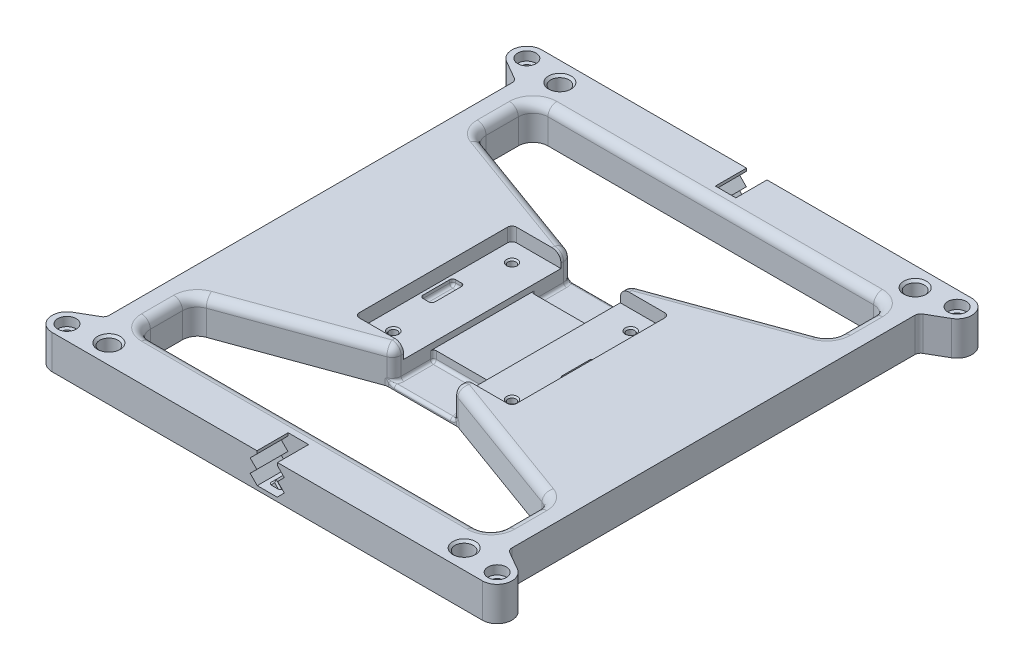
SolidWorks part; units mm, degrees
ref_plane "Front Plane" through (0, 0, 0) normal (0, 0, 1) x (1, 0, 0)
ref_plane "Top Plane" through (0, 0, 0) normal (0, 1, 0) x (1, 0, 0)
ref_plane "Right Plane" through (0, 0, 0) normal (1, 0, 0) x (0, 0, -1)
sketch "Sketch1" plane through (0, 0, 0) normal (0, 1, 0) x (1, 0, 0)
  line L0 (0, 0) -> (0, 67.5) construction
  line L1 (0, 67.5) -> (-67.875, 67.5) construction
  line L2 (-67.875, 67.5) -> (-67.875, 0)
  line L3 (-67.875, 0) -> (67.875, 0)
  line L4 (-67.875, 67.5) -> (-67.875, 80.5)
  line L5 (-65.875, 82.5) -> (65.875, 82.5)
  line L6 (0, 82.5) -> (0, 67.5) construction
  line L9 (67.875, 67.5) -> (67.875, 80.5)
  line L10 (67.875, 67.5) -> (67.875, 0)
  line L14 (-67.875, 70.5) -> (0, 70.5) construction
  circle A1 centre (-59.875, 76) radius 3.075 construction
  arc A11 (-67.875, 80.5) -> (-65.875, 82.5) centre (-65.875, 80.5) cw
  circle A12 centre (59.875, 76) radius 3.075 construction
  arc A13 (67.875, 80.5) -> (65.875, 82.5) centre (65.875, 80.5) ccw
  point P19 (67.875, 82.5)
  point P45 (-67.875, 82.5)
  dimension "D5" = 12
  dimension "D3" = 6.15
  dimension "D4" = 2
  dimension "D1" = 67.875
  dimension "D2" = 67.5
  dimension "D6" = 8
  dimension "D7" = 8.5
  dimension "D8" = 3
  dimension "D11" = 82.5
extrude "Boss-Extrude1" add sketch "Sketch1" along normal blind 11.5
sketch "Sketch3" plane through (0, 11.5, 0) normal (0, 1, 0) x (1, 0, 0)
  line L0 (0, 0) -> (-67.875, 0) construction
  line L2 (0, 0) -> (0, 82.5) construction
  line L3 (65.875, 82.5) -> (-65.875, 82.5) construction
  line L4 (3.96, -16.3) -> (3.96, 16.3)
  line L5 (-2.46, -17.8) -> (2.46, -17.8)
  line L6 (-3.96, 16.3) -> (-3.96, -16.3)
  line L7 (2.46, 17.8) -> (-2.46, 17.8)
  line L8 (0, 17.8) -> (0, -17.8) construction
  line L9 (-67.875, 80.5) -> (-67.875, 0) construction
  line L10 (-67.875, 0) -> (67.875, 0) construction
  arc A0 (-2.46, 17.8) -> (-3.96, 16.3) centre (-2.46, 16.3) ccw
  arc A1 (3.96, 16.3) -> (2.46, 17.8) centre (2.46, 16.3) ccw
  arc A2 (2.46, -17.8) -> (3.96, -16.3) centre (2.46, -16.3) ccw
  arc A3 (-3.96, -16.3) -> (-2.46, -17.8) centre (-2.46, -16.3) ccw
  point P9 (0, 0)
  point P23 (0, 0)
  dimension "D2" = 1.5
  dimension "D1" = 35.6
  dimension "D3" = 7.92
sketch "Sketch4" plane through (0, 11.5, 0) normal (0, 1, 0) x (1, 0, 0)
  circle A3 centre (59.875, 76) radius 3.075 construction
  circle A5 centre (-59.875, 76) radius 3.075 construction
  circle A10 centre (59.875, 76) radius 3.075
  circle A13 centre (-59.875, 76) radius 3.075
extrude "Cut-Extrude1" cut sketch "Sketch4" against normal blind 6
sketch "Sketch40" plane through (0, 0, -82.5) normal (0, 0, -1) x (-1, 0, 0)
  line L1 (5.55, 3.75) -> (3.3, 6) construction
  line L2 (5.55, 3.75) -> (3.3, 1.5) construction
  line L3 (0, 11.5) -> (0, 1.5) construction
  line L4 (0, 1.5) -> (3.3, 1.5) construction
  line L5 (3.3, 6) -> (5.55, 8.25) construction
  line L6 (3.3, 6) -> (3.3, 1.5) construction
  line L7 (5.55, 8.25) -> (3.3, 10.5) construction
  line L8 (3.3, 6) -> (3.3, 10.5) construction
  line L9 (5.55, 3.75) -> (5.55, 8.25) construction
  line L10 (3.3, 10.5) -> (3.3, 11.5) construction
  line L11 (3.3, 1.5) -> (5.55, 1.5) construction
  line L12 (5.55, 1.5) -> (5.55, 3.75) construction
  line L13 (5.55, 3.75) -> (3.3, 3.75) construction
  line L14 (5.55, 8.25) -> (3.3, 8.25) construction
  line L15 (3.3, 6) -> (5.55, 6) construction
  line L16 (-3.3, 11.5) -> (3.3, 11.5)
  line L17 (3.3621, 1.35) -> (-3.3621, 1.35)
  line L18 (0, 1.35) -> (0, 1.5) construction
  line L19 (-3.3, 11.5) -> (-3.45, 11.5)
  line L20 (-3.45, 10.5621) -> (-3.45, 11.5)
  line L22 (3.45, 10.5621) -> (3.45, 11.5)
  line L23 (5.7621, 8.25) -> (3.45, 10.5621)
  line L24 (3.5121, 6) -> (5.7621, 8.25)
  line L25 (5.7621, 3.75) -> (3.5121, 6)
  line L26 (5.7621, 3.75) -> (3.3621, 1.35)
  line L33 (3.3, 11.5) -> (3.45, 11.5)
  line L34 (-65.875, 11.5) -> (65.875, 11.5) construction
  line L35 (-5.7621, 8.25) -> (-3.45, 10.5621)
  line L36 (-3.5121, 6) -> (-5.7621, 8.25)
  line L37 (-5.7621, 3.75) -> (-3.5121, 6)
  line L38 (-5.7621, 3.75) -> (-3.3621, 1.35)
  dimension "D2" = 1
  dimension "D3" = 45
  dimension "D4" = 45
  dimension "D5" = 45
  dimension "D6" = 45
  dimension "D7" = 3.3
  dimension "D1" = 10
  dimension "D8" = 0.15
  dimension "D9" = 0.15
  dimension "D10" = 0.15
  dimension "D11" = 0.15
  dimension "D12" = 0.15
  dimension "D13" = 0.15
extrude "Cut-Extrude31" cut sketch "Sketch40" against normal blind 10.5
sketch "Sketch41" plane through (0, 0, -72) normal (0, 0, -1) x (-1, 0, 0)
  line L0 (0, 1.35) -> (0, 3.35) construction
  line L1 (-3.3621, 1.35) -> (3.3621, 1.35) construction
  line L2 (0, 3.35) -> (2, 1.35)
  line L3 (-3.3621, 1.35) -> (3.3621, 1.35) construction
  line L4 (2, 1.35) -> (-2, 1.35)
  line L5 (0, 3.35) -> (-2, 1.35)
  dimension "D1" = 45
  dimension "D2" = 2
extrude "Boss-Extrude9" add sketch "Sketch41" along normal blind 8
chamfer "Chamfer7" distance 0.5 angle 45 2 edges at (1, 2.35, -80) (-1, 2.35, -80)
mirror "Mirror1" about plane through (0, 0, 0) normal (0, 0, 1) of "Cut-Extrude1", "Boss-Extrude1", "Cut-Extrude31", "Boss-Extrude9", "Chamfer7"
sketch "Sketch28" plane through (0, 11.5, 0) normal (0, 1, 0) x (1, 0, 0)
  line L1 (-26, 26) -> (26, 26) construction
  line L2 (-26, 26) -> (-26, -26) construction
  line L3 (-26, -26) -> (26, -26) construction
  line L4 (26, 26) -> (26, -26) construction
  line L5 (-26, 26) -> (26, -26) construction
  line L6 (-26, -26) -> (26, 26) construction
  line L7 (-25, 26.5) -> (25, 26.5)
  line L8 (-26.5, 25) -> (-26.5, -25)
  line L9 (-25, -26.5) -> (25, -26.5)
  line L10 (26.5, 25) -> (26.5, -25)
  line L11 (-26.5, 26.5) -> (26.5, -26.5) construction
  line L12 (-26.5, -26.5) -> (26.5, 26.5) construction
  arc A0 (-25, -26.5) -> (-26.5, -25) centre (-25, -25) cw
  arc A1 (25, -26.5) -> (26.5, -25) centre (25, -25) ccw
  arc A2 (25, 26.5) -> (26.5, 25) centre (25, 25) cw
  arc A3 (-25, 26.5) -> (-26.5, 25) centre (-25, 25) ccw
  point P0 (0, 0)
  point P6 (0, 0)
  dimension "D4" = 1.5
  dimension "D1" = 52
  dimension "D2" = 0.5
  dimension "D3" = 0.5
extrude "Cut-Extrude21" cut sketch "Sketch28" against normal blind 4.6
sketch "Sketch36" plane through (0, 6.9, 0) normal (0, 1, 0) x (1, 0, 0)
  line L2 (-26, 26) -> (-26, -26) construction
  line L3 (-26, 26) -> (26, 26) construction
  circle A0 centre (-20, 20) radius 1.35
  circle A1 centre (20, 20) radius 1.35
  circle A2 centre (20, -20) radius 1.35
  circle A3 centre (-20, -20) radius 1.35
  point P15 (0, 0)
  dimension "D3" = 2.7
  dimension "D1" = 6
  dimension "D2" = 6
extrude "Cut-Extrude28" cut sketch "Sketch36" against normal blind 5
chamfer "Chamfer6" distance 0.5 angle 45 4 edges at (-20, 6.9, 21.35) (20, 6.9, 21.35) (20, 6.9, -18.65) (-20, 6.9, -18.65)
sketch "Sketch29" plane through (0, 6.9, 0) normal (0, 1, 0) x (1, 0, 0)
  line L0 (0, 0) -> (26.5, 0) construction
  line L5 (0, 0) -> (0, -26.5) construction
  line L6 (-25, -26.5) -> (25, -26.5) construction
  line L7 (26.5, -25) -> (26.5, 25) construction
  line L8 (-10, 26.5) -> (10, 16.5) construction
  line L9 (-10, 16.5) -> (10, 26.5) construction
  line L10 (-10, -16.5) -> (10, -16.5)
  line L11 (-10, -16.5) -> (-10, -26.5)
  line L12 (-10, -26.5) -> (10, -26.5)
  line L13 (10, -16.5) -> (10, -26.5)
  line L14 (-10, -16.5) -> (10, -26.5) construction
  line L15 (-10, -26.5) -> (10, -16.5) construction
  line L16 (10, 16.5) -> (10, 26.5)
  line L17 (-10, 26.5) -> (10, 26.5)
  line L18 (-10, 16.5) -> (-10, 26.5)
  line L19 (-10, 16.5) -> (10, 16.5)
  point P4 (0, -21.5)
  point P17 (0, 21.5)
  dimension "D1" = 20
  dimension "D2" = 10
extrude "Cut-Extrude22" cut sketch "Sketch29" against normal blind 5.5
sketch "Sketch25" plane through (0, 0, 0) normal (0, -1, 0) x (1, 0, 0)
  line L0 (0, 0) -> (67.875, 0) construction
  line L2 (0, 0) -> (0, 82.5) construction
  line L4 (75, 73.1699) -> (68.875, 69.6336)
  line L5 (72.5, 77.5) -> (67.875, 77.5) construction
  line L6 (67.875, 67.9016) -> (67.875, 80.5)
  line L8 (65.875, 82.5) -> (72.5, 82.5)
  line L9 (-72.5, 77.5) -> (-67.875, 77.5) construction
  line L10 (-65.875, 82.5) -> (-72.5, 82.5)
  line L11 (-67.875, 67.9016) -> (-67.875, 80.5)
  line L12 (-75, 73.1699) -> (-68.875, 69.6336)
  line L13 (-72.5, -77.5) -> (-67.875, -77.5) construction
  line L14 (72.5, -77.5) -> (67.875, -77.5) construction
  line L15 (-75, -73.1699) -> (-68.875, -69.6336)
  line L16 (-67.875, -67.9016) -> (-67.875, -80.5)
  line L17 (-65.875, -82.5) -> (-72.5, -82.5)
  line L18 (65.875, -82.5) -> (72.5, -82.5)
  line L19 (67.875, -67.9016) -> (67.875, -80.5)
  line L20 (75, -73.1699) -> (68.875, -69.6336)
  line L21 (67.875, 80.5) -> (67.875, -80.5) construction
  line L22 (65.875, 82.5) -> (-65.875, 82.5) construction
  circle A0 centre (72.5, 77.5) radius 1.7
  arc A1 (75, 73.1699) -> (72.5, 82.5) centre (72.5, 77.5) ccw
  arc A2 (68.875, 69.6336) -> (67.875, 67.9016) centre (69.875, 67.9016) ccw
  arc A17 (67.875, 80.5) -> (65.875, 82.5) centre (65.875, 80.5) ccw
  arc A18 (-67.875, 80.5) -> (-65.875, 82.5) centre (-65.875, 80.5) cw
  arc A19 (-68.875, 69.6336) -> (-67.875, 67.9016) centre (-69.875, 67.9016) cw
  arc A20 (-75, 73.1699) -> (-72.5, 82.5) centre (-72.5, 77.5) cw
  circle A21 centre (-72.5, 77.5) radius 1.7
  circle A22 centre (-72.5, -77.5) radius 1.7
  arc A23 (-75, -73.1699) -> (-72.5, -82.5) centre (-72.5, -77.5) ccw
  arc A24 (-68.875, -69.6336) -> (-67.875, -67.9016) centre (-69.875, -67.9016) ccw
  arc A25 (-67.875, -80.5) -> (-65.875, -82.5) centre (-65.875, -80.5) ccw
  arc A26 (67.875, -80.5) -> (65.875, -82.5) centre (65.875, -80.5) cw
  arc A27 (68.875, -69.6336) -> (67.875, -67.9016) centre (69.875, -67.9016) cw
  arc A28 (75, -73.1699) -> (72.5, -82.5) centre (72.5, -77.5) cw
  circle A29 centre (72.5, -77.5) radius 1.7
  arc A30 (67.875, 80.5) -> (65.875, 82.5) centre (65.875, 80.5) ccw construction
  dimension "D1" = 3.4
  dimension "D2" = 10
  dimension "D6" = 2
  dimension "D3" = 4.625
  dimension "D4" = 60
extrude "Boss-Extrude7" add sketch "Sketch25" against normal up to surface (11.5 mm away) up to face at (0, 11.5, 0)
sketch "Sketch27" plane through (0, 11.5, 0) normal (0, 1, 0) x (1, 0, 0)
  circle A4 centre (-72.5, -77.5) radius 3.1
  circle A5 centre (72.5, -77.5) radius 3.1
  circle A6 centre (-72.5, 77.5) radius 3.1
  circle A7 centre (72.5, 77.5) radius 3.1
  dimension "D1" = 6.2
extrude "Cut-Extrude20" cut sketch "Sketch27" against normal blind 3
sketch "Sketch37" plane through (0, 6.9, 0) normal (0, 1, 0) x (1, 0, 0)
  line L0 (67.875, 0) -> (0, 0) construction
  line L2 (0, 0) -> (-67.875, 0) construction
  line L3 (26.5, -25) -> (26.5, 25) construction
  line L4 (24.5, 5.5) -> (22.5, 5.5)
  line L5 (25.5, 4.5) -> (25.5, -4.5)
  line L6 (24.5, -5.5) -> (22.5, -5.5)
  line L7 (21.5, 4.5) -> (21.5, -4.5)
  line L8 (25.5, 5.5) -> (21.5, -5.5) construction
  line L9 (25.5, -5.5) -> (21.5, 5.5) construction
  line L10 (0, 0) -> (0, 26.5) construction
  line L11 (-10, 16.5) -> (10, 16.5) construction
  line L12 (-24.5, -5.5) -> (-22.5, -5.5)
  line L13 (-25.5, 4.5) -> (-25.5, -4.5)
  line L14 (-24.5, 5.5) -> (-22.5, 5.5)
  line L15 (-21.5, 4.5) -> (-21.5, -4.5)
  line L21 (10, 16.5) -> (10, -16.5)
  line L23 (25, 26.5) -> (-25, 26.5) construction
  line L24 (-10, 16.5) -> (10, 16.5)
  line L25 (-10, 16.5) -> (-10, -16.5)
  line L26 (-10, -16.5) -> (10, -16.5)
  line L27 (67.875, -67.9016) -> (67.875, 67.9016) construction
  arc A0 (22.5, -5.5) -> (21.5, -4.5) centre (22.5, -4.5) cw
  arc A1 (25.5, -4.5) -> (24.5, -5.5) centre (24.5, -4.5) cw
  arc A2 (22.5, 5.5) -> (21.5, 4.5) centre (22.5, 4.5) ccw
  arc A3 (24.5, 5.5) -> (25.5, 4.5) centre (24.5, 4.5) cw
  arc A4 (-22.5, 5.5) -> (-21.5, 4.5) centre (-22.5, 4.5) cw
  arc A5 (-24.5, 5.5) -> (-25.5, 4.5) centre (-24.5, 4.5) ccw
  arc A6 (-22.5, -5.5) -> (-21.5, -4.5) centre (-22.5, -4.5) ccw
  arc A7 (-25.5, -4.5) -> (-24.5, -5.5) centre (-24.5, -4.5) ccw
  point P5 (23.5, 0)
  point P54 (10, 0)
  point P56 (-10, 0)
  dimension "D4" = 1
  dimension "D1" = 11
  dimension "D2" = 4
  dimension "D3" = 3
extrude "Cut-Extrude29" cut sketch "Sketch37" against normal blind 2
fillet "Fillet20" radius 1 16 edges at (25.2071, 4.9, -5.2071) (25.5, 4.9, 0) (25.2071, 4.9, 5.2071) (23.5, 4.9, 5.5) (21.7929, 4.9, 5.2071) (21.5, 4.9, 0) (21.7929, 4.9, -5.2071) (-21.7929, 4.9, -5.2071) (-21.5, 4.9, 0) (-21.7929, 4.9, 5.2071) (-23.5, 4.9, 5.5) (-25.2071, 4.9, 5.2071) (-25.5, 4.9, 0) (-25.2071, 4.9, -5.2071) (23.5, 4.9, -5.5) (-23.5, 4.9, -5.5)
sketch "Sketch38" plane through (0, 11.5, 0) normal (0, 1, 0) x (1, 0, 0)
  line L0 (11.9739, -30.2185) -> (56.5851, -46.4556)
  line L1 (59.875, -51.1541) -> (59.875, -62)
  line L2 (54.875, -67) -> (-54.875, -67)
  line L3 (0, -67) -> (0, -26.5) construction
  line L4 (-10, -26.5) -> (10, -26.5) construction
  line L7 (-3.45, -72) -> (3.45, -72) construction
  line L9 (-25, -26.5) -> (25, -26.5) construction
  line L12 (0, 0) -> (67.875, 0) construction
  line L13 (0, 67) -> (0, 26.5) construction
  line L20 (10, -27.3994) -> (10, -26.5)
  line L21 (10, -26.5) -> (25, -26.5) construction
  line L22 (10, -26.5) -> (-10, -26.5)
  line L23 (10, -26.5) -> (10, 26.5) construction
  line L24 (-10, -27.3994) -> (-10, -26.5)
  line L25 (-59.875, -51.1541) -> (-59.875, -62)
  line L26 (-11.9739, -30.2185) -> (-56.5851, -46.4556)
  line L35 (67.875, -67.9016) -> (67.875, 67.9016) construction
  line L36 (-11.9739, 30.2185) -> (-56.5851, 46.4556)
  line L37 (-59.875, 51.1541) -> (-59.875, 62)
  line L38 (-10, 27.3994) -> (-10, 26.5)
  line L39 (10, 26.5) -> (-10, 26.5)
  line L40 (10, 27.3994) -> (10, 26.5)
  line L41 (54.875, 67) -> (-54.875, 67)
  line L42 (59.875, 51.1541) -> (59.875, 62)
  line L43 (11.9739, 30.2185) -> (56.5851, 46.4556)
  arc A0 (59.875, -51.1541) -> (56.5851, -46.4556) centre (54.875, -51.1541) ccw
  arc A1 (59.875, -62) -> (54.875, -67) centre (54.875, -62) cw
  arc A8 (11.9739, -30.2185) -> (10, -27.3994) centre (13, -27.3994) cw
  arc A9 (-11.9739, -30.2185) -> (-10, -27.3994) centre (-13, -27.3994) ccw
  arc A10 (-59.875, -62) -> (-54.875, -67) centre (-54.875, -62) ccw
  arc A11 (-59.875, -51.1541) -> (-56.5851, -46.4556) centre (-54.875, -51.1541) cw
  arc A18 (-59.875, 51.1541) -> (-56.5851, 46.4556) centre (-54.875, 51.1541) ccw
  arc A19 (-59.875, 62) -> (-54.875, 67) centre (-54.875, 62) cw
  arc A20 (-11.9739, 30.2185) -> (-10, 27.3994) centre (-13, 27.3994) cw
  arc A21 (11.9739, 30.2185) -> (10, 27.3994) centre (13, 27.3994) ccw
  arc A22 (59.875, 62) -> (54.875, 67) centre (54.875, 62) ccw
  arc A23 (59.875, 51.1541) -> (56.5851, 46.4556) centre (54.875, 51.1541) cw
  point P49 (10, -29.5)
  point P60 (-10, -29.5)
  point P66 (-10, 29.5)
  point P67 (10, 29.5)
  dimension "D4" = 5
  dimension "D6" = 3
  dimension "D1" = 5
  dimension "D2" = 8
  dimension "D3" = 20
  dimension "D5" = 3
extrude "Cut-Extrude30" cut sketch "Sketch38" against normal through all
sketch "Sketch39" plane through (0, 0, 0) normal (0, -1, 0) x (1, 0, 0)
  line L0 (0, 0) -> (67.875, 0) construction
  line L2 (-11.9739, 30.2185) -> (11.9739, 30.2185)
  line L3 (10, 27.3994) -> (10, 26.5) construction
  line L4 (10, 26.5) -> (-10, 26.5) construction
  line L5 (-10, 26.5) -> (-10, 27.3994) construction
  line L6 (10, 27.3994) -> (10, 26.5)
  line L7 (10, 26.5) -> (-10, 26.5)
  line L8 (-10, 26.5) -> (-10, 27.3994)
  line L9 (-10, -26.5) -> (-10, -27.3994)
  line L10 (10, -26.5) -> (-10, -26.5)
  line L11 (10, -27.3994) -> (10, -26.5)
  line L12 (-11.9739, -30.2185) -> (11.9739, -30.2185)
  line L13 (67.875, 67.9016) -> (67.875, -67.9016) construction
  arc A0 (11.9739, 30.2185) -> (10, 27.3994) centre (13, 27.3994) ccw construction
  arc A1 (-10, 27.3994) -> (-11.9739, 30.2185) centre (-13, 27.3994) ccw construction
  arc A2 (11.9739, 30.2185) -> (10, 27.3994) centre (13, 27.3994) ccw
  arc A3 (-10, 27.3994) -> (-11.9739, 30.2185) centre (-13, 27.3994) ccw
  arc A4 (-10, -27.3994) -> (-11.9739, -30.2185) centre (-13, -27.3994) cw
  arc A5 (11.9739, -30.2185) -> (10, -27.3994) centre (13, -27.3994) cw
extrude "Boss-Extrude8" add sketch "Sketch39" against normal up to surface (1.4 mm away) up to face at (0, 1.4, 21.5)
fillet "Fillet21" radius 1 14 edges at (0, 1.4, -16.5) (0, 1.4, 16.5) (-10.5425, 1.4, 29.1201) (10.5425, 1.4, 29.1201) (-10, 3.15, 16.5) (-10, 1.4, 21.9497) (10, 3.15, 16.5) (10, 1.4, 21.9497) (-10, 1.4, -21.9497) (-10, 3.15, -16.5) (10, 3.15, -16.5) (10, 1.4, -21.9497) (-10.5425, 1.4, -29.1201) (10.5425, 1.4, -29.1201)
fillet "Fillet22" radius 3 26 edges at (-10, 11.5, 26.9497) (-10.5425, 11.5, 29.1201) (10, 11.5, 26.9497) (10.5425, 11.5, 29.1201) (34.2795, 11.5, 38.337) (58.9708, 11.5, 48.2862) (59.875, 11.5, 56.577) (58.4105, 11.5, 65.5355) (0, 11.5, 67) (-58.4105, 11.5, 65.5355) (-59.875, 11.5, 56.577) (-58.9708, 11.5, 48.2862) (-34.2795, 11.5, 38.337) (10, 11.5, -26.9497) (10.5425, 11.5, -29.1201) (34.2795, 11.5, -38.337) (58.9708, 11.5, -48.2862) (59.875, 11.5, -56.577) (58.4105, 11.5, -65.5355) (0, 11.5, -67) (-58.4105, 11.5, -65.5355) (-59.875, 11.5, -56.577) (-58.9708, 11.5, -48.2862) (-10, 11.5, -26.9497) (-10.5425, 11.5, -29.1201) (-34.2795, 11.5, -38.337)
fillet "Fillet24" radius 3 4 edges at (-11.9739, 1.2, 30.2185) (11.9739, 1.2, 30.2185) (11.9739, 1.2, -30.2185) (-11.9739, 1.2, -30.2185)
fillet "Fillet25" radius 1 10 edges at (0, 1.4, 30.2185) (0, 1.4, -30.2185) (12.1079, 2.1665, 30.2926) (10.8141, 1.4985, 30.2185) (-12.1976, 2.1847, 30.3144) (-10.9036, 1.5265, 30.2185) (-10.8141, 1.4985, -30.2185) (10.9036, 1.5265, -30.2185) (-12.1079, 2.1665, -30.2926) (12.1976, 2.1847, -30.3144)
chamfer "Chamfer8" distance 0.75 angle 45 4 edges at (-59.875, 11.5, 72.925) (59.875, 11.5, 72.925) (-59.875, 11.5, -72.925) (59.875, 11.5, -72.925)
equation "\"D3@Sketch28\"=\"D2@Sketch28\""
equation "\"D2@Sketch36\"=\"D1@Sketch36\""
equation "\"D9@Sketch40\"=\"D8@Sketch40\""
equation "\"D10@Sketch40\"=\"D8@Sketch40\""
equation "\"D11@Sketch40\"=\"D8@Sketch40\""
equation "\"D12@Sketch40\"=\"D8@Sketch40\""
equation "\"D13@Sketch40\"=\"D8@Sketch40\""
